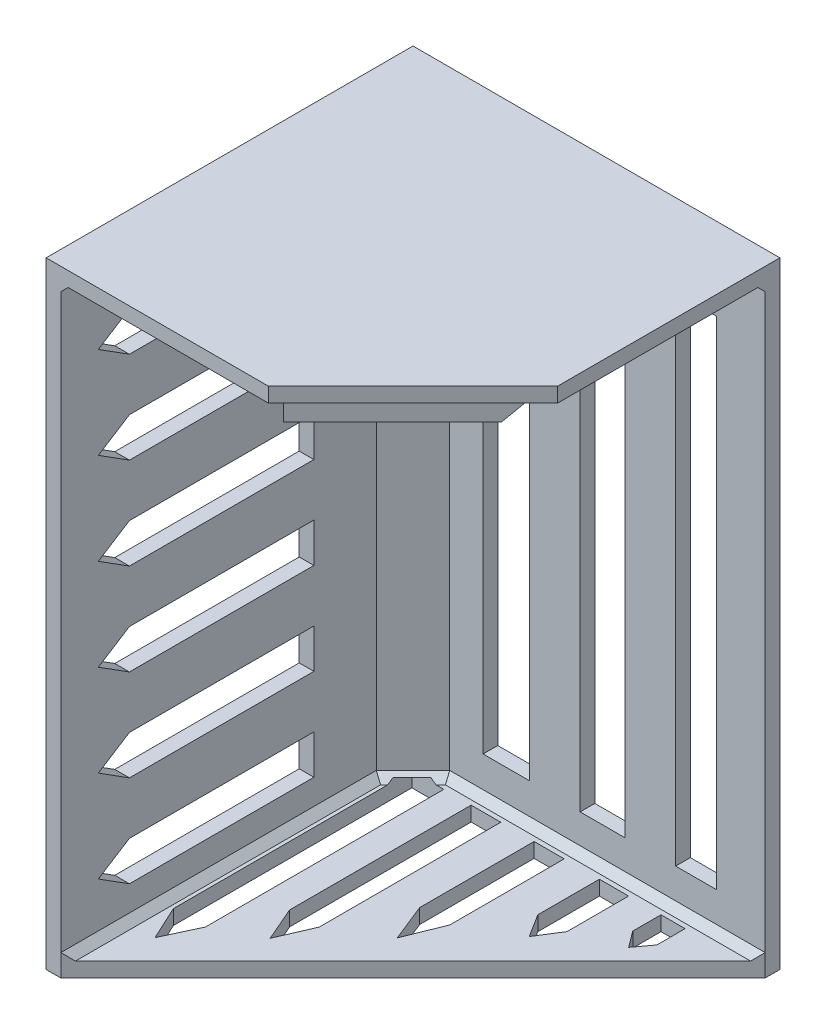
SolidWorks part; units mm, degrees
ref_plane "前视基准面" through (0, 0, 0) normal (0, 0, 1) x (1, 0, 0)
ref_plane "上视基准面" through (0, 0, 0) normal (0, 1, 0) x (1, 0, 0)
ref_plane "右视基准面" through (0, 0, 0) normal (1, 0, 0) x (0, 0, -1)
other "Configuration Table"
sketch "草图1" plane through (0, 0, 0) normal (0, 1, 0) x (1, 0, 0)
  line L1 (0, 0) -> (100, 0)
  line L2 (0, 0) -> (0, -100)
  line L3 (0, -100) -> (4, -100)
  line L4 (100, 0) -> (100, -4)
  line L7 (100, -4) -> (4, -4)
  line L8 (4, -100) -> (4, -4)
  dimension "D1" = 100
  dimension "D2" = 100
  dimension "D3" = 4
  dimension "D4" = 4
extrude "凸台-拉伸1" add sketch "草图1" along normal blind 168
chamfer "倒角1" distance 10 angle 45 1 edges at (4, 84, 4)
sketch "草图2" plane through (0, 168, 0) normal (0, 1, 0) x (1, 0, 0)
  line L0 (100, -4) -> (4, -100)
  line L1 (4, -100) -> (4, -14)
  line L2 (4, -14) -> (14, -4)
  line L3 (14, -4) -> (100, -4)
extrude "凸台-拉伸2" add sketch "草图2" against normal blind 4
sketch "草图3" plane through (0, 0, 0) normal (0, -1, 0) x (-1, 0, 0)
  line L0 (-4, -100) -> (-4, -14)
  line L1 (-4, -14) -> (-14, -4)
  line L2 (-14, -4) -> (-100, -4)
  line L3 (-100, -4) -> (-4, -100)
extrude "凸台-拉伸3" add sketch "草图3" against normal blind 4
sketch "草图4" plane through (0, 168, 0) normal (0, 1, 0) x (1, 0, 0)
  line L0 (100, -4) -> (100, -60.5685)
  line L1 (60.5685, -100) -> (4, -100)
  line L2 (4, -100) -> (100, -4)
  line L3 (60.5685, -100) -> (100, -60.5685)
  dimension "D1" = 40
extrude "凸台-拉伸4" add sketch "草图4" against normal blind 4
sketch "草图5" plane through (0, 164, 0) normal (0, -1, 0) x (-1, 0, 0)
  line L0 (-59.1277, -94.3698) -> (-94.483, -59.0144)
  line L1 (-94.483, -59.0144) -> (-83.1693, -47.7007)
  line L2 (-83.1693, -47.7007) -> (-47.814, -83.0561)
  line L3 (-47.814, -83.0561) -> (-59.1277, -94.3698)
  line L5 (-60.5685, -100) -> (-100, -60.5685) construction
  dimension "D1" = 50
  dimension "D2" = 16
  dimension "D3" = 5
extrude "凸台-拉伸5" add sketch "草图5" along normal blind 8
chamfer "倒角3" distance 8 angle 45 1 edges at (88.8262, 156, 53.3576)
chamfer "倒角4" distance 8 angle 45 1 edges at (62.6632, 156, 68.2068)
chamfer "倒角6" distance 1 angle 45 1 edges at (83.1693, 160, 53.3576) first distance on face at (66.9059, 160, 69.6211)
chamfer "倒角7" distance 2 angle 45 6 edges at (4, 4, 57) (9, 4, 9) (57, 4, 4) (4, 164, 57) (9, 164, 9) (57, 164, 4)
sketch "草图6" plane through (0, 0, 4) normal (0, 0, 1) x (1, 0, 0)
  line L1 (23.1026, 149.7888) -> (35.7859, 149.7888)
  line L2 (23.1026, 149.7888) -> (23.1026, 14.4272)
  line L3 (23.1026, 14.4272) -> (35.7859, 14.4272)
  line L4 (35.7859, 149.7888) -> (35.7859, 14.4272)
  line L5 (49.5626, 149.3515) -> (61.8086, 149.3515)
  line L6 (49.5626, 149.3515) -> (49.5626, 13.9899)
  line L7 (49.5626, 13.9899) -> (61.8086, 13.9899)
  line L8 (61.8086, 149.3515) -> (61.8086, 13.9899)
  line L9 (75.5853, 149.5701) -> (86.7379, 149.5701)
  line L10 (75.5853, 149.5701) -> (75.5853, 14.2086)
  line L11 (75.5853, 14.2086) -> (86.7379, 14.2086)
  line L12 (86.7379, 149.5701) -> (86.7379, 14.2086)
extrude "切除-拉伸1" cut sketch "草图6" against normal blind 5
sketch "草图7" plane through (4, 0, 0) normal (1, 0, 0) x (0, 0, -1)
  line L1 (-81.2915, 23.6124) -> (-31.0098, 23.6124)
  line L3 (-81.2915, 12.8885) -> (-31.0098, 12.8885)
  line L4 (-31.0098, 23.6124) -> (-31.0098, 12.8885)
  line L24 (-89.7677, 18.2504) -> (-81.2915, 12.8885)
  line L25 (-89.7677, 18.2504) -> (-81.2915, 23.6124)
  line L26 (-81.2915, 37.8885) -> (-31.0098, 37.8885)
  line L27 (-31.0098, 48.6124) -> (-31.0098, 37.8885)
  line L28 (-81.2915, 48.6124) -> (-31.0098, 48.6124)
  line L29 (-89.7677, 43.2504) -> (-81.2915, 48.6124)
  line L30 (-89.7677, 43.2504) -> (-81.2915, 37.8885)
  line L31 (-81.2915, 62.8885) -> (-31.0098, 62.8885)
  line L32 (-31.0098, 73.6124) -> (-31.0098, 62.8885)
  line L33 (-81.2915, 73.6124) -> (-31.0098, 73.6124)
  line L34 (-89.7677, 68.2504) -> (-81.2915, 73.6124)
  line L35 (-89.7677, 68.2504) -> (-81.2915, 62.8885)
  line L36 (-81.2915, 87.8885) -> (-31.0098, 87.8885)
  line L37 (-31.0098, 98.6124) -> (-31.0098, 87.8885)
  line L38 (-81.2915, 98.6124) -> (-31.0098, 98.6124)
  line L39 (-89.7677, 93.2504) -> (-81.2915, 98.6124)
  line L40 (-89.7677, 93.2504) -> (-81.2915, 87.8885)
  line L41 (-81.2915, 112.8885) -> (-31.0098, 112.8885)
  line L42 (-31.0098, 123.6124) -> (-31.0098, 112.8885)
  line L43 (-81.2915, 123.6124) -> (-31.0098, 123.6124)
  line L44 (-89.7677, 118.2504) -> (-81.2915, 123.6124)
  line L45 (-89.7677, 118.2504) -> (-81.2915, 112.8885)
  line L46 (-81.2915, 137.8885) -> (-31.0098, 137.8885)
  line L47 (-31.0098, 148.6124) -> (-31.0098, 137.8885)
  line L48 (-81.2915, 148.6124) -> (-31.0098, 148.6124)
  line L49 (-89.7677, 143.2504) -> (-81.2915, 148.6124)
  line L50 (-89.7677, 143.2504) -> (-81.2915, 137.8885)
  dimension "D1" = 6
extrude "切除-拉伸2" cut sketch "草图7" against normal blind 5
sketch "草图8" plane through (0, 0, 0) normal (0, -1, 0) x (-1, 0, 0)
  line L0 (-11.3138, -81.6209) -> (-6.9589, -72.2798)
  line L2 (-6.9589, -72.2798) -> (-6.9589, -7.2707)
  line L3 (-6.9589, -7.2707) -> (-15.6688, -7.2707)
  line L4 (-15.6688, -72.2798) -> (-15.6688, -7.2707)
  line L5 (-11.3138, -81.6209) -> (-15.6688, -72.2798)
  line L6 (-27.1559, -66.0945) -> (-23.1165, -56.7534)
  line L8 (-23.1165, -56.7534) -> (-23.1165, -7.2707)
  line L9 (-23.1165, -7.2707) -> (-31.1953, -7.2707)
  line L10 (-31.1953, -56.7534) -> (-31.1953, -7.2707)
  line L11 (-27.1559, -66.0945) -> (-31.1953, -56.7534)
  line L12 (-44.3864, -48.6746) -> (-40.2839, -38.4498)
  line L14 (-40.2839, -38.4498) -> (-40.2839, -7.2707)
  line L15 (-40.2839, -7.2707) -> (-48.4889, -7.2707)
  line L16 (-48.4889, -38.4498) -> (-48.4889, -7.2707)
  line L18 (-48.4889, -38.4498) -> (-44.3864, -48.6746)
  line L19 (-62.0588, -30.371) -> (-58.0825, -24.0595)
  line L21 (-58.0825, -24.0595) -> (-58.0825, -7.2707)
  line L22 (-58.0825, -7.2707) -> (-66.0351, -7.2707)
  line L23 (-66.0351, -24.0595) -> (-66.0351, -7.2707)
  line L25 (-66.0351, -24.0595) -> (-62.0588, -30.371)
  line L26 (-78.1533, -19.3889) -> (-74.8713, -14.9708)
  line L28 (-74.8713, -14.9708) -> (-74.8713, -7.2707)
  line L29 (-74.8713, -7.2707) -> (-81.4353, -7.2707)
  line L30 (-81.4353, -14.9708) -> (-81.4353, -7.2707)
  line L32 (-81.4353, -14.9708) -> (-78.1533, -19.3889)
extrude "切除-拉伸3" cut sketch "草图8" against normal blind 5
equation "\"D4@草图1\"=\"D3@草图1\""
